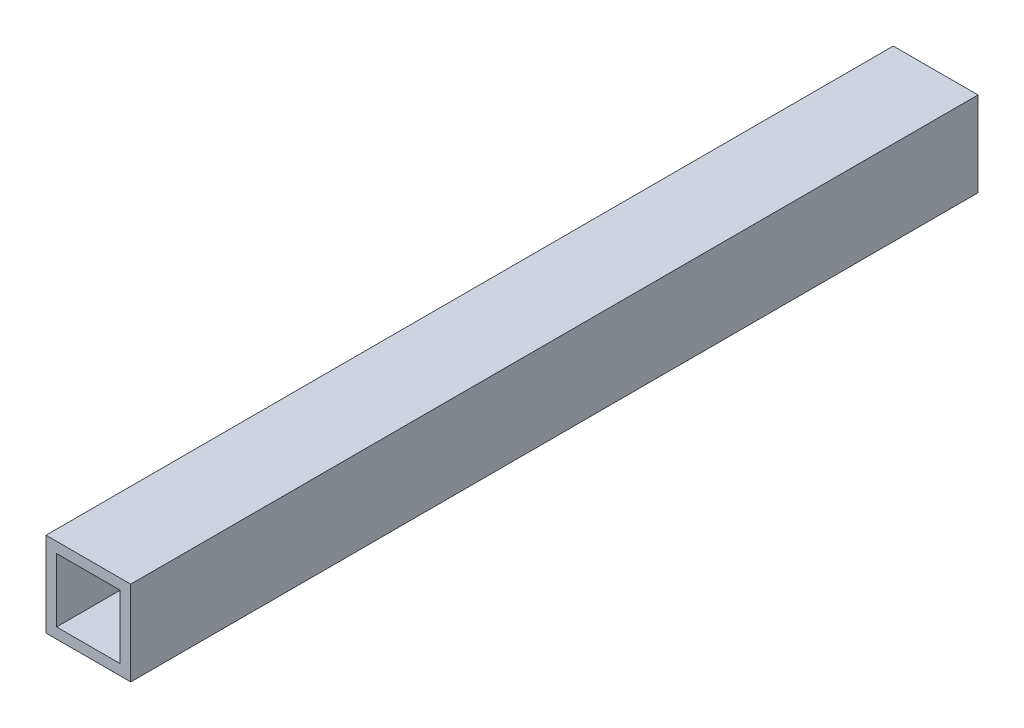
SolidWorks part; units mm, degrees
ref_plane "Front Plane" through (0, 0, 0) normal (0, 0, 1) x (1, 0, 0)
ref_plane "Top Plane" through (0, 0, 0) normal (0, 1, 0) x (1, 0, 0)
ref_plane "Right Plane" through (0, 0, 0) normal (1, 0, 0) x (0, 0, -1)
sketch "Sketch1" plane through (0, 0, 0) normal (0, 0, 1) x (1, 0, 0)
  line L0 (12.7, 0) -> (9.525, 0) construction
  line L1 (-12.7, 0) -> (12.7, 0) construction
  line L2 (0, 12.7) -> (0, -12.7)
  point P7 (0, 0)
sketch "Sketch2" plane through (0, 0, 0) normal (1, 0, 0) x (0, 0, -1)
  line L0 (127, 0) -> (-127, 0)
  point P4 (0, 0)
  dimension "Length" = 254
sketch "Sketch3" plane through (0, 0, 0) normal (0, 0, 1) x (1, 0, 0)
  line L0 (-12.7, 0) -> (12.7, 0) construction
  line L5 (12.7, -12.7) -> (-12.7, -12.7)
  line L6 (12.7, -12.7) -> (12.7, 12.7)
  line L11 (12.7, 12.7) -> (-12.7, 12.7)
  line L12 (-12.7, -12.7) -> (-12.7, 12.7)
  line L14 (12.7, -12.7) -> (-12.7, 12.7) construction
  line L15 (12.7, 12.7) -> (-12.7, -12.7) construction
  line L16 (9.525, -9.525) -> (-9.525, -9.525)
  line L17 (9.525, -9.525) -> (9.525, 9.525)
  line L18 (9.525, 9.525) -> (-9.525, 9.525)
  line L19 (-9.525, -9.525) -> (-9.525, 9.525)
  line L20 (9.525, -9.525) -> (-9.525, 9.525) construction
  line L21 (9.525, 9.525) -> (-9.525, -9.525) construction
  point P0 (0, 0)
  point P5 (0, 0)
  point P13 (9.525, -12.7)
  dimension "D1" = 3.175
extrude "Boss-Extrude1" add sketch "Sketch3" along normal up to vertex (127 mm away) and the other way up to vertex (127 mm away) up to point (0, 0, 127) other way up to point (0, 0, -127)
sketch "Sketch5" plane through (0, 0, 0) normal (1, 0, 0) x (0, 0, -1)
  line L0 (-127, 0) -> (127, 0) construction
  line L3 (-127, -12.7) -> (-127, 12.7) construction
  line L4 (127, -12.7) -> (127, 12.7) construction
  point P6 (-98.425, 0)
  point P7 (-88.9, 0)
  point P8 (88.9, 0)
  point P10 (98.425, 0)
  dimension "D1" = 28.575
  dimension "D2" = 38.1
  dimension "D3" = 28.575
  dimension "D4" = 38.1
equation "\"D1@Sketch3\"=\"Wall thickness@Sketch1\""
equation "\"D1@Sketch5\"=\"Width@Sketch1\"*1.125"
equation "\"D2@Sketch5\"=\"Width@Sketch1\"*1.5"
equation "\"D3@Sketch5\"=\"D1@Sketch5\""
equation "\"D4@Sketch5\"=\"D2@Sketch5\""
equation "\"D2@Sketch3\"=\"Wall Thickness@Sketch1\""
